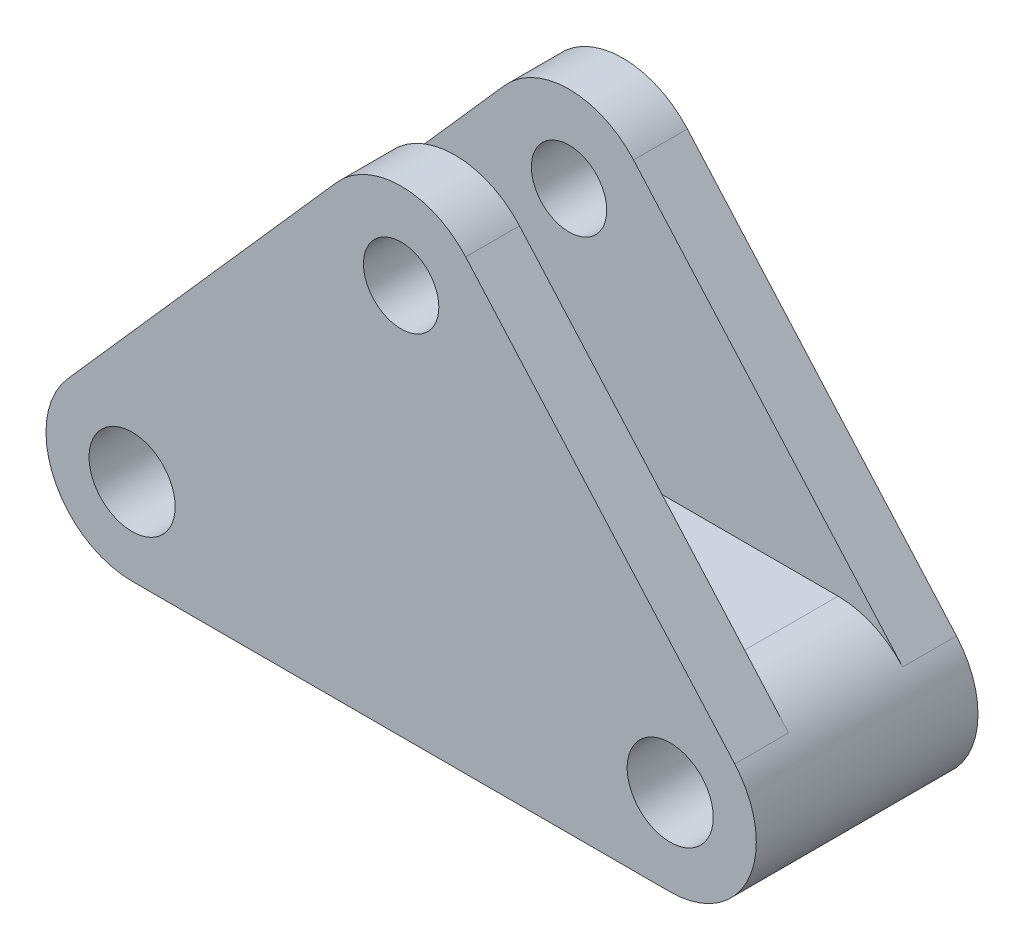
SolidWorks part; units mm, degrees
material "ABS"
ref_plane "Front Plane" through (0, 0, 0) normal (0, 0, 1) x (1, 0, 0)
ref_plane "Top Plane" through (0, 0, 0) normal (0, 1, 0) x (1, 0, 0)
ref_plane "Right Plane" through (0, 0, 0) normal (1, 0, 0) x (0, 0, -1)
sketch "Sketch1" plane through (0, 0, 0) normal (0, 0, 1) x (1, 0, 0)
  line L0 (0, 27.2364) -> (0, -32.7408) construction
  line L1 (25, -36.3) -> (-25, -36.3)
  line L2 (-30.9956, -23.0035) -> (-5.9956, 5.2965)
  line L3 (30.9956, -23.0035) -> (5.9956, 5.2965)
  line L4 (-25, -20.3) -> (25, -20.3)
  circle A0 centre (0, 0) radius 3.5
  circle A1 centre (0, 0) radius 11 construction
  circle A2 centre (-25, -28.3) radius 4
  arc A3 (-25, -36.3) -> (-30.9956, -23.0035) centre (-25, -28.3) cw
  arc A4 (-5.9956, 5.2965) -> (5.9956, 5.2965) centre (0, 0) cw
  arc A5 (25, -36.3) -> (30.9956, -23.0035) centre (25, -28.3) ccw
  circle A6 centre (25, -28.3) radius 4
  arc A7 (-25, -20.3) -> (-30.9956, -23.0035) centre (-25, -28.3) ccw
  arc A8 (25, -20.3) -> (30.9956, -23.0035) centre (25, -28.3) cw
  point P8 (0, 11)
  point P15 (0, -36.3)
  point P21 (0, -20.3)
  dimension "D1" = 7
  dimension "D2" = 22
  dimension "D3" = 8
  dimension "D6" = 8
  dimension "D7" = 8
  dimension "D4" = 25
  dimension "D5" = 39.3
extrude "Boss-Extrude1" add sketch "Sketch1" against normal blind 5 contours L0 L4 A7 A3 L1 A2 | L4 L0 L1 A5 A8 A6 | A1 L0 L4 A8 L3 | A4 L0 A0 A1 L3 | L0 A4 L2 A1 A0 | L0 A1 L2 A7 L4 region at (0, -28.3, 0) region at (0, -10.356, 0)
extrude "Boss-Extrude2" add sketch "Sketch1<3>" against normal blind 10.6 from vertex contours L0 L4 A7 A3 L1 A2 | L4 L0 L1 A5 A8 A6 region at (0, -28.3, 0) starting at point (-30.9956, -23.0035, -5)
sketch "Sketch1<3>" plane through (0, 0, 0) normal (0, 0, 1) x (1, 0, 0) same geometry as "Sketch1"
extrude "Boss-Extrude3" add sketch "Sketch1<4>" against normal blind 5 from vertex contours L0 A1 L2 A7 L4 | L0 A4 L2 A1 A0 | A4 L0 A0 A1 L3 | A1 L0 L4 A8 L3 | L4 L0 L1 A5 A8 A6 | L0 L4 A7 A3 L1 A2 region at (0, -28.3, 0) region at (0, -10.356, 0) starting at point (-25, -36.3, -15.6)
sketch "Sketch1<4>" plane through (0, 0, 0) normal (0, 0, 1) x (1, 0, 0) same geometry as "Sketch1"
equation "\"rod_diameter\"= 8"
equation "\"rod_hole_thickness\"= 4"
equation "\"rod_radius\"= \"rod_diameter\" / 2"
equation "\"platter_diameter\"= 320"
equation "\"platter_radius\"= \"platter_diameter\" / 2"
equation "\"extruder_mount_hole_spacing\"= 75"
equation "\"arm_rod_spacing\"= 40"
equation "\"top_frame_rod_spacing\"= \"arm_rod_spacing\" + 40"
equation "\"motor_level_rod_spacing\"= 15"
equation "\"linear_bearing_diameter\"= 15"
equation "\"z_rod_spacing\"= 75"
equation "\"platter_rod_spacing\"= 50"
equation "\"rod_nut_thickness\"= 6.5"
equation "\"rod_nut_inscribed_diameter\"= 13"
equation "\"z_height\"= 350"
equation "\"D1@Sketch1\"=\"rod_diameter\"-1"
equation "\"D3@Sketch1\"=\"rod_diameter\""
equation "\"D4@Sketch1\"=\"platter_rod_spacing\"/2"
equation "\"D6@Sketch1\"=\"rod_radius\"+\"rod_hole_thickness\""
equation "\"D7@Sketch1\"=\"rod_radius\"+\"rod_hole_thickness\""
